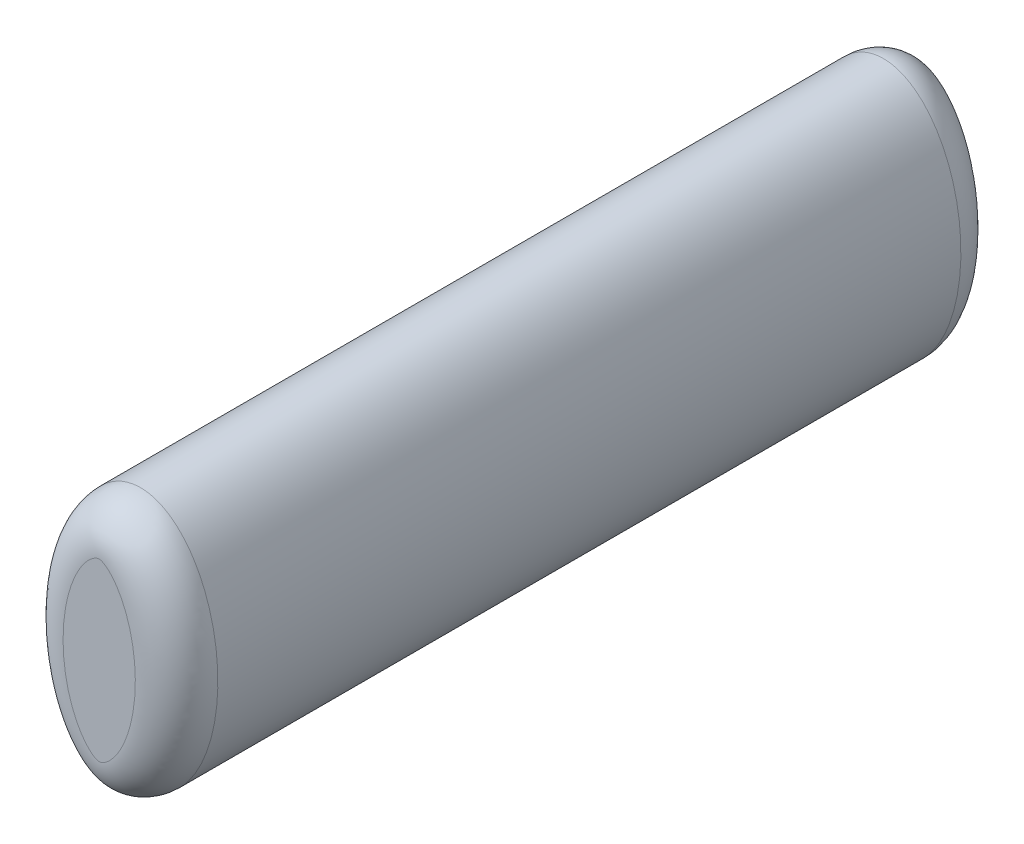
SolidWorks part; units mm, degrees
ref_plane "Ebene vorne" through (0, 0, 0) normal (0, 0, 1) x (1, 0, 0)
ref_plane "Ebene oben" through (0, 0, 0) normal (0, 1, 0) x (1, 0, 0)
ref_plane "Ebene rechts" through (0, 0, 0) normal (1, 0, 0) x (0, 0, -1)
sketch "Skizze1" plane through (0, 0, 0) normal (0, 0, 1) x (1, 0, 0)
  line L4 (0, 12.5) -> (0, 0)
  line L9 (0, 0) -> (-7.5, 0)
  ellipse E0 centre (0, 0) end of major axis (0, 12.5) minor radius 7.5 (0, 12.5) -> (-7.5, 0) ccw
  dimension "D3" = 25
  dimension "D4" = 15
extrude "Aufsatz-Linear austragen2" add sketch "Skizze1" along normal blind 80
sketch "Skizze4" plane through (0, 0, 0) normal (1, 0, 0) x (0, 0, -1)
  line L0 (-80, 0) -> (0, 0) construction
  line L1 (0, 0) -> (-40, 0)
  line L2 (0, 0) -> (0, 5)
  line L3 (0, 5) -> (-40, 5)
  line L4 (-40, 0) -> (-40, 5)
  dimension "D1" = 5
  dimension "D2" = 40
extrude "Schnitt-Linear austragen1" cut sketch "Skizze4" against normal blind 1.5
fillet "Verrundung2" radius 4 2 edges at (-5.3033, 8.8388, 0) (-5.3033, 8.8388, 80)
mirror "Spiegeln1" about plane through (0, 0, 80) normal (0, 1, 0) of bodies 103
mirror "Spiegeln2" about plane through (0, 12.5, 80) normal (-1, 0, 0) of bodies 104
